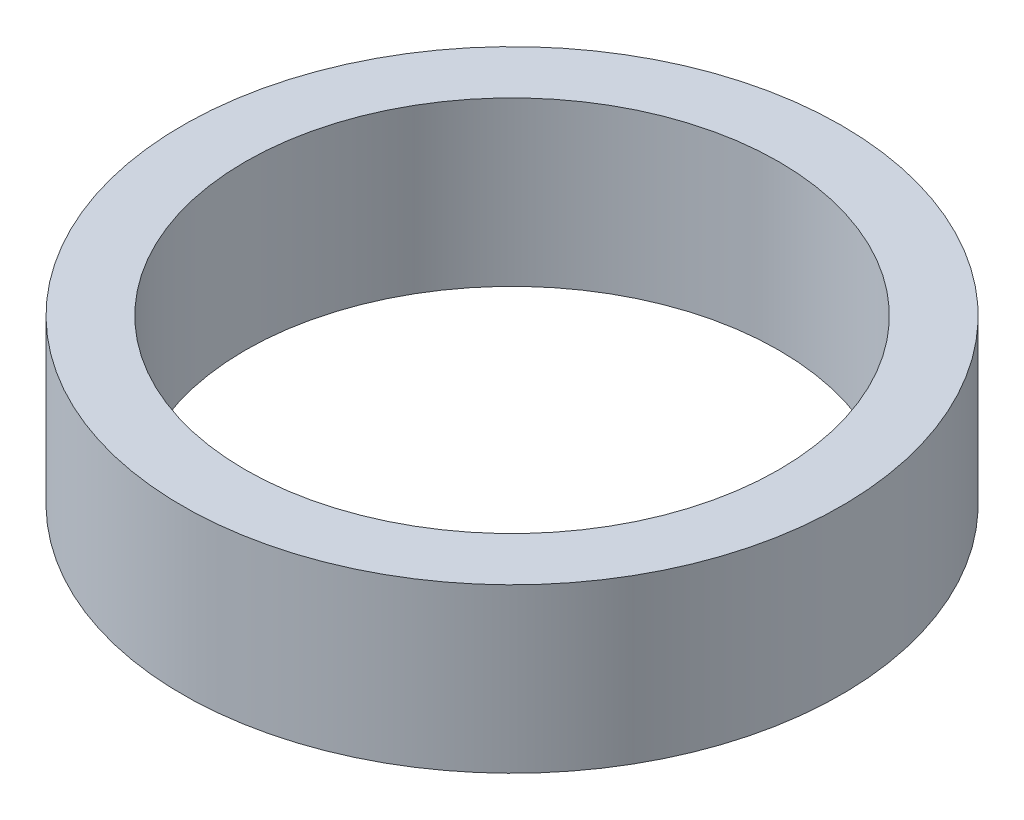
SolidWorks part; units mm, degrees
ref_plane "Front Plane" through (0, 0, 0) normal (0, 0, 1) x (1, 0, 0)
ref_plane "Top Plane" through (0, 0, 0) normal (0, 1, 0) x (1, 0, 0)
ref_plane "Right Plane" through (0, 0, 0) normal (1, 0, 0) x (0, 0, -1)
sketch "Sketch1" plane through (0, 0, 0) normal (0, 1, 0) x (1, 0, 0)
  circle A0 centre (0, 0) radius 52.5
  dimension "FLANGE_OD" = 105
extrude "Boss-Extrude1" add sketch "Sketch1" along normal blind 26
sketch "Sketch2" plane through (0, 0, 0) normal (0, 1, 0) x (1, 0, 0)
  circle A0 centre (0, 0) radius 42.5
  dimension "BORE_D" = 85
extrude "Cut-Extrude1" cut sketch "Sketch2" along normal through all
sketch "Sketch3" plane through (0, 26, 0) normal (0, 1, 0) x (1, 0, 0)
  circle A0 centre (0, 0) radius 23.4469 construction
  circle A1 centre (-23.4469, 0) radius 1.6689
  dimension "BOLT_D" = 3.3378
  dimension "BOLT_PCD" = 46.8938
extrude "Cut-Extrude2" cut sketch "Sketch3" against normal blind 16.4545 rebuild error yes
pattern_circular "CirPattern1" count 5 over 360 rebuild error yes
